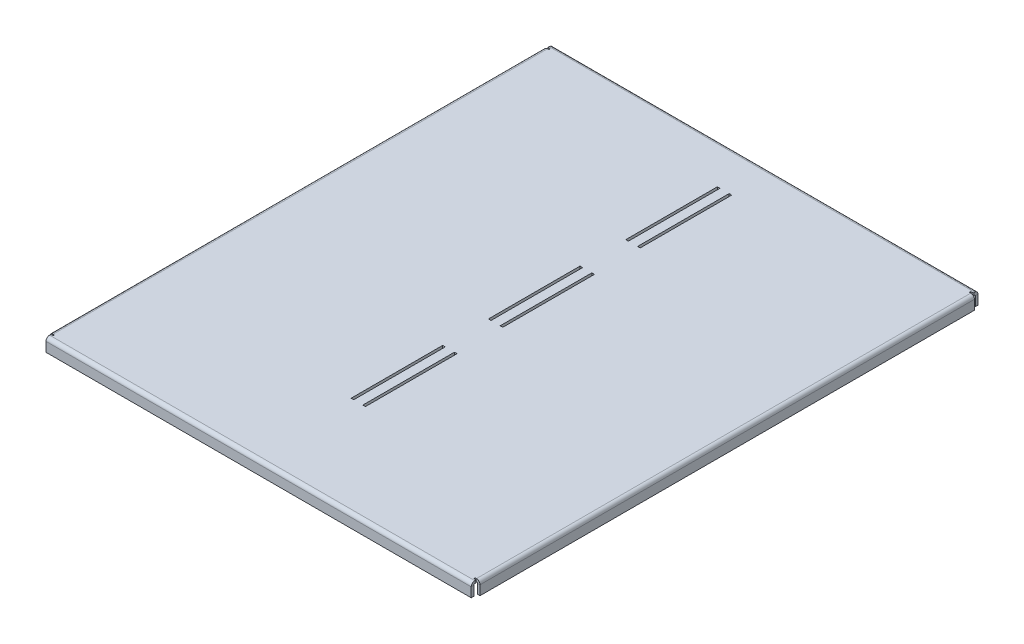
SolidWorks part; units mm, degrees
note: The reader was unsure of these and kept them because the rebuilt part matched: flange length of "Edge-Flange1", "Edge-Flange2", "Edge-Flange3", "Edge-Flange4".
material "ASTM A36 Steel"
ref_plane "Front Plane" through (0, 0, 0) normal (0, 0, 1) x (1, 0, 0)
ref_plane "Top Plane" through (0, 0, 0) normal (0, 1, 0) x (1, 0, 0)
ref_plane "Right Plane" through (0, 0, 0) normal (1, 0, 0) x (0, 0, -1)
sketch "Sketch1" plane through (0, 0, 0) normal (0, 0, 1) x (1, 0, 0)
  line L1 (-162.5, 5) -> (162.5, 5)
  line L2 (-162.5, 5) -> (-162.5, -5)
  line L3 (-162.5, -5) -> (162.5, -5)
  line L4 (162.5, 5) -> (162.5, -5)
  line L5 (-162.5, 5) -> (162.5, -5) construction
  line L6 (-162.5, -5) -> (162.5, 5) construction
  point P0 (0, 0)
  dimension "D1" = 10
  dimension "D2" = 325
base flange "Base-Flange1" sketch "Sketch1" thickness 2 reverse thickness direction no parameters "D1"=0.7366
edge flange "Edge-Flange1" sketch "Sketch4" flange angle 90 flange length 387.4 flange position material inside bend radius 0.7366 thickness 2 relief rectangular parameters "D6"=10
sketch "Sketch4" plane through (0, 5, -2) normal (0, 1, 0) x (1, 0, 0)
  line L0 (162.5, 0) -> (-162.5, 0) construction
  line L1 (162.5, 0) -> (-162.5, 0)
  line L2 (-162.5, 0) -> (-162.5, 385.4)
  line L3 (-162.5, 385.4) -> (162.5, 385.4)
  line L4 (162.5, 385.4) -> (162.5, 0)
bend "EdgeBend1" bend radius 0.7366 bend angle 90 parameters "D5"=1
edge flange "Edge-Flange2" sketch "Sketch7" flange angle 90 flange length 10 flange position material inside bend radius 0.7366 thickness 2 relief rectangular parameters "D6"=10
sketch "Sketch7" plane through (0, 3, -387.4) normal (0, 0, -1) x (1, 0, 0)
  line L0 (162.5, 0) -> (-162.5, 0) construction
  line L1 (162.5, 0) -> (-162.5, 0)
  line L2 (-162.5, 0) -> (-162.5, 8)
  line L3 (-162.5, 8) -> (162.5, 8)
  line L4 (162.5, 8) -> (162.5, 0)
bend "EdgeBend2" bend radius 0.7366 bend angle 90 parameters "D5"=2
edge flange "Edge-Flange3" sketch "Sketch10" flange angle 90 flange length 10 flange position material outside bend radius 0.7366 thickness 2 relief rectangular parameters "D6"=10
sketch "Sketch10" plane through (162.5, 3, 0) normal (1, 0, 0) x (0, 0, 1)
  line L0 (-2.7366, 0) -> (-384.6634, 0) construction
  line L1 (-4.7366, 0) -> (-382.6634, 0)
  line L2 (-382.6634, 0) -> (-382.6634, 8)
  line L3 (-382.6634, 8) -> (-4.7366, 8)
  line L4 (-4.7366, 8) -> (-4.7366, 0)
  dimension "D1" = 2
  dimension "D2" = 2
bend "EdgeBend3" bend radius 0.7366 bend angle 90 parameters "D5"=3
edge flange "Edge-Flange4" sketch "Sketch13" flange angle 90 flange length 10 flange position material outside bend radius 0.7366 thickness 2 relief rectangular parameters "D6"=10
sketch "Sketch13" plane through (-162.5, 3, 0) normal (-1, 0, 0) x (0, 0, -1)
  line L0 (384.6634, 0) -> (2.7366, 0) construction
  line L1 (382.6634, 0) -> (4.7366, 0)
  line L2 (4.7366, 0) -> (4.7366, 8)
  line L3 (4.7366, 8) -> (382.6634, 8)
  line L4 (382.6634, 8) -> (382.6634, 0)
  line L5 (4.7366, 0.7366) -> (4.7366, 8) construction
  line L8 (382.6634, 8) -> (382.6634, 0.7366) construction
bend "EdgeBend4" bend radius 0.7366 bend angle 90 parameters "D5"=4
sketch "Sketch14" plane through (0, 5, 0) normal (0, 1, 0) x (1, 0, 0)
  line L1 (5.5, 377.4) -> (-5.5, 377.4) construction
  line L2 (5.5, 377.4) -> (5.5, 55) construction
  line L3 (5.5, 55) -> (-5.5, 55) construction
  line L4 (-5.5, 377.4) -> (-5.5, 55) construction
  line L5 (5.5, 377.4) -> (-5.5, 55) construction
  line L6 (5.5, 55) -> (-5.5, 377.4) construction
  line L8 (-5.5, 146.2) -> (-5.5, 76.2)
  line L9 (-5.5, 251.2) -> (-3.5, 251.2)
  line L10 (-5.5, 251.2) -> (-5.5, 181.2)
  line L11 (-5.5, 181.2) -> (-3.5, 181.2)
  line L12 (-3.5, 251.2) -> (-3.5, 181.2)
  line L13 (-5.5, 146.2) -> (-3.5, 146.2)
  line L14 (-3.5, 146.2) -> (-3.5, 76.2)
  line L15 (-5.5, 76.2) -> (-3.5, 76.2)
  line L16 (-5.5, 251.2) -> (-5.5, 181.2)
  line L17 (-5.5, 251.2) -> (-3.5, 251.2)
  line L18 (-3.5, 251.2) -> (-3.5, 181.2)
  line L19 (-5.5, 181.2) -> (-3.5, 181.2)
  line L20 (-5.5, 356.2) -> (-5.5, 286.2)
  line L21 (-5.5, 356.2) -> (-3.5, 356.2)
  line L22 (-3.5, 356.2) -> (-3.5, 286.2)
  line L23 (-5.5, 286.2) -> (-3.5, 286.2)
  line L24 (0, 363.5607) -> (0, 216.2) construction
  line L25 (5.5, 146.2) -> (3.5, 146.2)
  line L26 (3.5, 146.2) -> (3.5, 76.2)
  line L27 (5.5, 76.2) -> (3.5, 76.2)
  line L28 (5.5, 146.2) -> (5.5, 76.2)
  line L29 (5.5, 356.2) -> (3.5, 356.2)
  line L30 (3.5, 356.2) -> (3.5, 286.2)
  line L31 (5.5, 286.2) -> (3.5, 286.2)
  line L32 (5.5, 356.2) -> (5.5, 286.2)
  line L33 (5.5, 181.2) -> (3.5, 181.2)
  line L34 (3.5, 251.2) -> (3.5, 181.2)
  line L35 (5.5, 251.2) -> (3.5, 251.2)
  line L36 (5.5, 251.2) -> (5.5, 181.2)
  line L37 (162.5, 387.4) -> (-162.5, 387.4) construction
  point P0 (0, 216.2)
  dimension "D1" = 322.4
  dimension "D2" = 11
  dimension "D3" = 10
  dimension "D4" = 70
  dimension "D5" = 2
  dimension "D6" = 35
  dimension "D7" = 2
  dimension "D8" = 2
extrude "Cut-Extrude1" cut sketch "Sketch14" against normal through all both and the other way through all contours L20 L23 L22 L21 | L32 L29 L30 L31 | L12 L9 L10 L11 | L36 L35 L34 L33 | L8 L15 L14 L13 | L28 L25 L26 L27 normal cut yes
sketch "Bend-Lines1" [suppressed] plane through (0, 0, 0) normal (0, 1, 0) x (1, 0, 0)
sketch "Bounding-Box1" [suppressed] plane through (0, 0, 0) normal (0, 1, 0) x (1, 0, 0)
sheet metal parameters "Sheet-Metal1" thickness 2 parameters "D1"=0.7366
flat pattern "Flat-Pattern1" [suppressed]
sketch "Bend-Lines2" plane through (0, 0, 0) normal (0, 1, 0) x (1, 0, 0)
sketch3d "Bounding-Box2" [suppressed]
  line L0 (-148.5, -5, 0) -> (148.5, -5, 0) construction
  line L1 (-148.5, 5, 0) -> (148.5, 5, 0) construction
  line L2 (-148.5, -5, 0) -> (-148.5, 5, 0) construction
  line L3 (148.5, -5, 0) -> (148.5, 5, 0) construction
sheet metal parameters "Sheet-Metal6" thickness 2 parameters "D1"=0.7366
flat pattern "Flat-Pattern1"
sketch "Bend-Lines2" plane through (0, 0, 0) normal (0, 0, 1) x (1, 0, 0)
  line L0 (148.5, 3.6273) -> (-148.5, 3.6273) construction
  line L1 (148.5, 3.6273) -> (-148.5, 3.6273) construction
sketch3d "Bounding-Box2" [suppressed]
  line L0 (148.5, 344.4546, 0) -> (148.5, -5, 0) construction
  line L1 (-148.5, 344.4546, 0) -> (-148.5, -5, 0) construction
  line L2 (148.5, 344.4546, 0) -> (-148.5, 344.4546, 0) construction
  line L3 (148.5, -5, 0) -> (-148.5, -5, 0) construction
bend of the flat pattern "Flatten-<EdgeBend1>1"
sheet metal parameters "Sheet-Metal7" thickness 2 parameters "D1"=0.7366
flat pattern "Flat-Pattern1"
sketch "Bend-Lines2" plane through (0, 0, 0) normal (0, 0, 1) x (1, 0, 0)
  line L0 (164.5, 3.6273) -> (-164.5, 3.6273) construction
  line L1 (164.5, 3.6273) -> (-164.5, 3.6273) construction
  line L2 (164.5, 343.282) -> (-164.5, 343.282) construction
  line L3 (164.5, 343.282) -> (-164.5, 343.282) construction
sketch3d "Bounding-Box2" [suppressed]
  line L0 (164.5, 351.9093, 0) -> (164.5, -5, 0) construction
  line L1 (-164.5, 351.9093, 0) -> (-164.5, -5, 0) construction
  line L2 (164.5, 351.9093, 0) -> (-164.5, 351.9093, 0) construction
  line L3 (164.5, -5, 0) -> (-164.5, -5, 0) construction
bend of the flat pattern "Flatten-<EdgeBend1>1"
bend of the flat pattern "Flatten-<EdgeBend2>1"
sheet metal parameters "Sheet-Metal8" thickness 2 parameters "D1"=0.7366
flat pattern "Flat-Pattern1"
sketch "Bend-Lines2" plane through (0, 0, 0) normal (0, 0, 1) x (1, 0, 0)
  line L0 (164.5, 3.6273) -> (-164.5, 3.6273) construction
  line L1 (164.5, 3.6273) -> (-164.5, 3.6273) construction
  line L2 (164.5, 343.282) -> (-164.5, 343.282) construction
  line L3 (164.5, 343.282) -> (-164.5, 343.282) construction
  line L4 (163.1273, 6.9912) -> (163.1273, 339.918) construction
  line L5 (163.1273, 6.9912) -> (163.1273, 339.918) construction
sketch3d "Bounding-Box2" [suppressed]
  line L0 (171.7546, 351.9093, 0) -> (171.7546, -5, 0) construction
  line L1 (-164.5, 351.9093, 0) -> (-164.5, -5, 0) construction
  line L2 (171.7546, 351.9093, 0) -> (-164.5, 351.9093, 0) construction
  line L3 (171.7546, -5, 0) -> (-164.5, -5, 0) construction
bend of the flat pattern "Flatten-<EdgeBend1>1"
bend of the flat pattern "Flatten-<EdgeBend2>1"
bend of the flat pattern "Flatten-<EdgeBend3>1"
sheet metal parameters "Sheet-Metal9" thickness 2 parameters "D1"=0.7366
flat pattern "Flat-Pattern1"
sketch "Bend-Lines2" plane through (0, 0, 0) normal (0, 0, 1) x (1, 0, 0)
  line L0 (162.5, 3.6273) -> (-162.5, 3.6273) construction
  line L1 (162.5, 3.6273) -> (-162.5, 3.6273) construction
  line L2 (162.5, 388.282) -> (-162.5, 388.282) construction
  line L3 (162.5, 388.282) -> (-162.5, 388.282) construction
  line L4 (163.1273, 6.9912) -> (163.1273, 384.918) construction
  line L5 (163.1273, 6.9912) -> (163.1273, 384.918) construction
  line L6 (-163.1273, 384.918) -> (-163.1273, 6.9912) construction
  line L7 (-163.1273, 384.918) -> (-163.1273, 6.9912) construction
sketch3d "Bounding-Box2" [suppressed]
  line L0 (171.7546, 396.9093, 0) -> (171.7546, -5, 0) construction
  line L1 (-171.7546, 396.9093, 0) -> (-171.7546, -5, 0) construction
  line L2 (171.7546, 396.9093, 0) -> (-171.7546, 396.9093, 0) construction
  line L3 (171.7546, -5, 0) -> (-171.7546, -5, 0) construction
bend of the flat pattern "Flatten-<EdgeBend1>1"
bend of the flat pattern "Flatten-<EdgeBend2>1"
bend of the flat pattern "Flatten-<EdgeBend3>1"
bend of the flat pattern "Flatten-<EdgeBend4>1"
sheet metal parameters "Sheet-Metal10" thickness 2 parameters "D1"=0.7366
flat pattern "Flat-Pattern1"
sketch "Bend-Lines2" plane through (0, 0, 0) normal (0, 0, 1) x (1, 0, 0)
  line L0 (162.5, 3.6273) -> (-162.5, 3.6273) construction
  line L1 (162.5, 3.6273) -> (-162.5, 3.6273) construction
  line L2 (162.5, 388.282) -> (-162.5, 388.282) construction
  line L3 (162.5, 388.282) -> (-162.5, 388.282) construction
  line L4 (163.1273, 6.9912) -> (163.1273, 384.918) construction
  line L5 (163.1273, 6.9912) -> (163.1273, 384.918) construction
  line L6 (-163.1273, 384.918) -> (-163.1273, 6.9912) construction
  line L7 (-163.1273, 384.918) -> (-163.1273, 6.9912) construction
sketch3d "Bounding-Box2" [suppressed]
  line L0 (171.7546, 396.9093, 0) -> (171.7546, -5, 0) construction
  line L1 (-171.7546, 396.9093, 0) -> (-171.7546, -5, 0) construction
  line L2 (171.7546, 396.9093, 0) -> (-171.7546, 396.9093, 0) construction
  line L3 (171.7546, -5, 0) -> (-171.7546, -5, 0) construction
bend of the flat pattern "Flatten-<EdgeBend1>1"
bend of the flat pattern "Flatten-<EdgeBend2>1"
bend of the flat pattern "Flatten-<EdgeBend3>1"
bend of the flat pattern "Flatten-<EdgeBend4>1"
